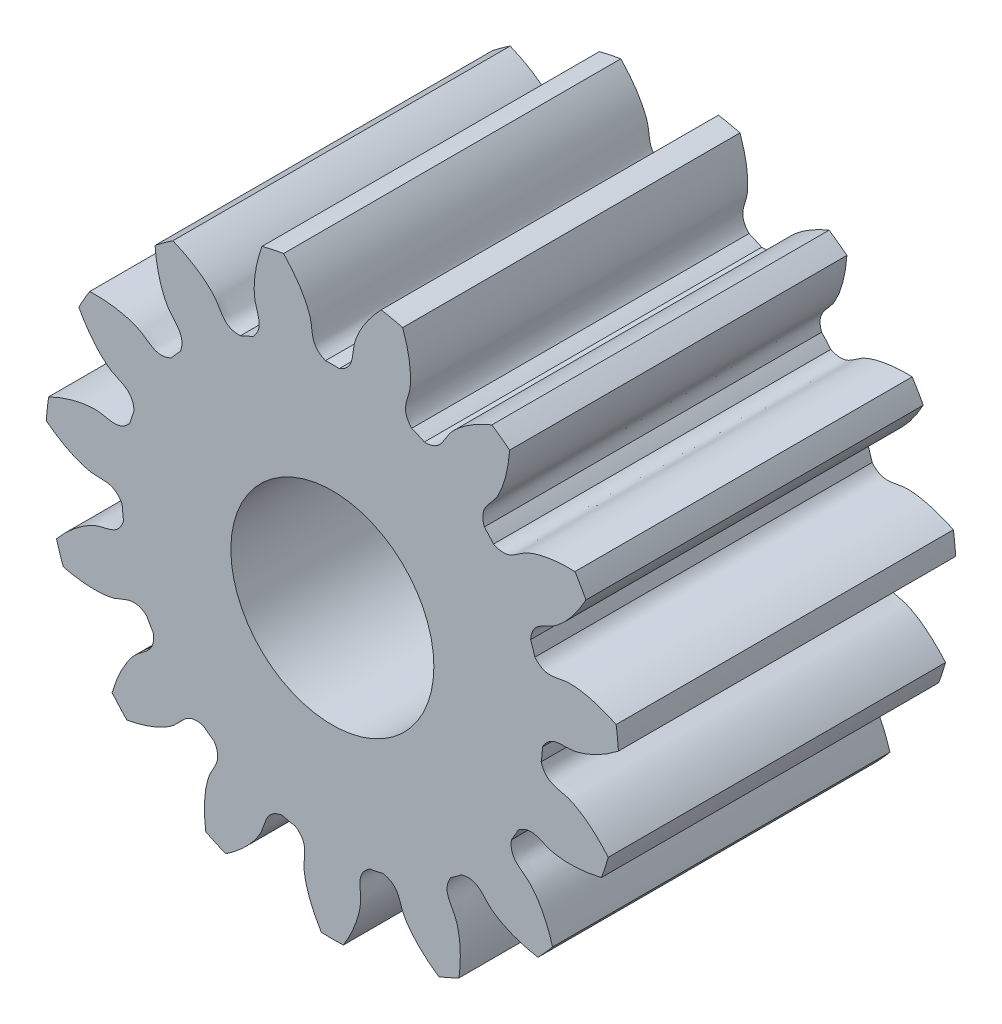
SolidWorks part; units mm, degrees
material "黄铜"
ref_plane "前视基准面" through (0, 0, 0) normal (0, 0, 1) x (1, 0, 0)
ref_plane "上视基准面" through (0, 0, 0) normal (0, 1, 0) x (1, 0, 0)
ref_plane "右视基准面" through (0, 0, 0) normal (1, 0, 0) x (0, 0, -1)
sketch "草图1" plane through (0, 0, 0) normal (0, 0, 1) x (1, 0, 0)
  circle A0 centre (0, 0) radius 4.25
extrude "凸台-拉伸1" add sketch "草图1" along normal blind 5
ref_axis "基准轴1" through (0, 0, 5) along (0, 0, -1)
sketch "草图2" plane through (0, 0, 0) normal (0, 0, 1) x (1, 0, 0)
  line L0 (0, 0) -> (0, 4.25) construction
  circle A0 centre (0, 0) radius 4.25 construction
  arc A1 (0.1021, 3.1233) -> (-0.1021, 3.1233) centre (0, 0) ccw
  arc A2 (1.6234, 4.818) -> (-1.6234, 4.818) centre (0, 0) ccw
  spline S0 degree 3 poles (0.1021, 3.1233) (0.3286, 3.2172) (0.2861, 3.3932) (0.3256, 3.5543) (0.3287, 3.5658) (0.3324, 3.5787) (0.3368, 3.5928) (0.3419, 3.6082) (0.3478, 3.6248) (0.3545, 3.6426) (0.3621, 3.6616) (0.3706, 3.6817) (0.3801, 3.703) (0.3906, 3.7253) (0.4022, 3.7486) (0.4149, 3.773) (0.4288, 3.7984) (0.4438, 3.8247) (0.4601, 3.8519) (0.4777, 3.8799) (0.4967, 3.9088) (0.517, 3.9385) (0.5387, 3.9689) (0.5618, 4) (0.5865, 4.0317) (0.6126, 4.064) (0.6403, 4.0969) (0.6696, 4.1303) (0.7005, 4.1641) (0.733, 4.1983) (0.7673, 4.2329) (0.8032, 4.2678) (0.8408, 4.3029) (0.8801, 4.3381) (0.9213, 4.3735) (0.9642, 4.409) (1.0089, 4.4445) (1.0555, 4.4799) (1.1039, 4.5153) (1.1541, 4.5504) (1.2062, 4.5854) (1.2602, 4.62) (1.316, 4.6543) (1.3738, 4.6882) (1.4334, 4.7216) (1.5163, 4.7659) (1.5801, 4.7975) (1.6234, 4.818) knots 0 0 0 0 0.202473 0.206979 0.212085 0.217793 0.224101 0.23101 0.23852 0.24663 0.255341 0.264653 0.274566 0.285079 0.296194 0.307909 0.320225 0.333141 0.346659 0.360777 0.375496 0.390816 0.406736 0.423257 0.440379 0.458102 0.476426 0.49535 0.514875 0.535001 0.555728 0.577055 0.598984 0.621513 0.644642 0.668373 0.692704 0.717636 0.743169 0.769303 0.796037 0.823373 0.851309 0.879845 0.908983 0.938721 1 1 1 1
  spline S1 degree 3 poles (-0.1021, 3.1233) (-0.3286, 3.2172) (-0.2861, 3.3932) (-0.3256, 3.5543) (-0.3287, 3.5658) (-0.3324, 3.5787) (-0.3368, 3.5928) (-0.3419, 3.6082) (-0.3478, 3.6248) (-0.3545, 3.6426) (-0.3621, 3.6616) (-0.3706, 3.6817) (-0.3801, 3.703) (-0.3906, 3.7253) (-0.4022, 3.7486) (-0.4149, 3.773) (-0.4288, 3.7984) (-0.4438, 3.8247) (-0.4601, 3.8519) (-0.4777, 3.8799) (-0.4967, 3.9088) (-0.517, 3.9385) (-0.5387, 3.9689) (-0.5618, 4) (-0.5865, 4.0317) (-0.6126, 4.064) (-0.6403, 4.0969) (-0.6696, 4.1303) (-0.7005, 4.1641) (-0.733, 4.1983) (-0.7673, 4.2329) (-0.8032, 4.2678) (-0.8408, 4.3029) (-0.8801, 4.3381) (-0.9213, 4.3735) (-0.9642, 4.409) (-1.0089, 4.4445) (-1.0555, 4.4799) (-1.1039, 4.5153) (-1.1541, 4.5504) (-1.2062, 4.5854) (-1.2602, 4.62) (-1.316, 4.6543) (-1.3738, 4.6882) (-1.4334, 4.7216) (-1.5163, 4.7659) (-1.5801, 4.7975) (-1.6234, 4.818) knots 0 0 0 0 0.202473 0.206979 0.212085 0.217793 0.224101 0.23101 0.23852 0.24663 0.255341 0.264653 0.274566 0.285079 0.296194 0.307909 0.320225 0.333141 0.346659 0.360777 0.375496 0.390816 0.406736 0.423257 0.440379 0.458102 0.476426 0.49535 0.514875 0.535001 0.555728 0.577055 0.598984 0.621513 0.644642 0.668373 0.692704 0.717636 0.743169 0.769303 0.796037 0.823373 0.851309 0.879845 0.908983 0.938721 1 1 1 1
extrude "切除-拉伸1" cut sketch "草图2" along normal through all
pattern_circular "阵列(圆周)1" count 15 over 360 about axis through (0, 0, 5) along (0, 0, -1) of "切除-拉伸1"
sketch "草图3" plane through (0, 0, 0) normal (0, 0, 1) x (1, 0, 0)
  circle A0 centre (0, 0) radius 3.75 construction
  dimension "Dn" = 7.5
sketch "草图4" plane through (0, 0, 0) normal (0, 0, 1) x (1, 0, 0)
  circle A0 centre (0, 0) radius 1.505
  dimension "D1" = 3.01
extrude "切除-拉伸2" cut sketch "草图4" along normal through all
sketch "草图5" plane through (0, 0, 0) normal (0, 0, 1) x (1, 0, 0)
  line L0 (0, 0) -> (4.2267, 0.4442) construction
  arc A0 (4.2407, 0.2816) -> (4.2065, 0.6063) centre (0, 0) ccw construction
